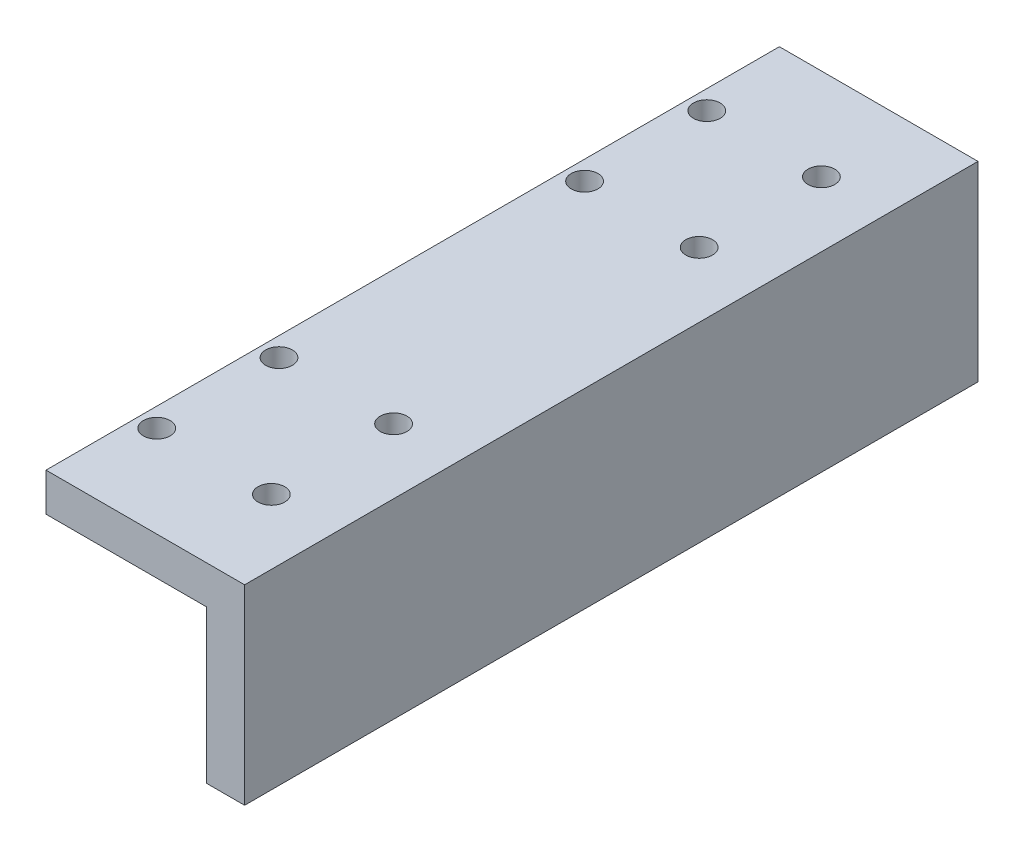
SolidWorks part; units mm, degrees
ref_plane "Front Plane" through (0, 0, 0) normal (0, 0, 1) x (1, 0, 0)
ref_plane "Top Plane" through (0, 0, 0) normal (0, 1, 0) x (1, 0, 0)
ref_plane "Right Plane" through (0, 0, 0) normal (1, 0, 0) x (0, 0, -1)
sketch "Sketch1" plane through (0, 0, 0) normal (0, 1, 0) x (1, 0, 0)
  line L0 (0, 48) -> (0, -48) construction
  line L1 (-10, 48) -> (10, 48)
  line L2 (-10, 48) -> (-10, -48)
  line L3 (-10, -48) -> (10, -48)
  line L4 (10, 48) -> (10, -48) construction
  line L5 (-10, 48) -> (10, -48) construction
  line L6 (-10, -48) -> (10, 48) construction
  line L7 (-7.5, 36) -> (7.5, 36) construction
  line L8 (-7.5, 36) -> (7.5, 20) construction
  line L9 (-10, 0) -> (10, 0) construction
  line L10 (-7.5, -36) -> (7.5, -20) construction
  line L11 (-7.5, -36) -> (7.5, -36) construction
  line L12 (-7.5, 20) -> (7.5, 20) construction
  line L13 (10, 48) -> (11, 48)
  line L14 (11, 48) -> (11, -48)
  line L15 (11, -48) -> (10, -48)
  circle A0 centre (-7.5, 36) radius 1.75
  circle A1 centre (7.5, 36) radius 1.75
  circle A2 centre (-7.5, 20) radius 1.75
  circle A3 centre (7.5, 20) radius 1.75
  circle A4 centre (7.5, -20) radius 1.75
  circle A5 centre (-7.5, -20) radius 1.75
  circle A6 centre (7.5, -36) radius 1.75
  circle A7 centre (-7.5, -36) radius 1.75
  point P0 (0, 0)
  point P16 (0, 36)
  dimension "D2" = 3.5
  dimension "D1" = 20
  dimension "D3" = 15
  dimension "D4" = 16
  dimension "D5" = 12
  dimension "D6" = 20
  dimension "D7" = 1
extrude "Boss-Extrude1" add sketch "Sketch1" along normal blind 5
sketch "Sketch2" plane through (11, 0, 0) normal (1, 0, 0) x (0, 0, -1)
  line L1 (-48, 5) -> (48, 5)
  line L2 (-48, 5) -> (-48, -20)
  line L3 (-48, -20) -> (48, -20)
  line L5 (48, 5) -> (48, -20)
  line L6 (48, 5) -> (48, 0) construction
  line L7 (-48, 5) -> (-48, 0) construction
  line L8 (-48, 5) -> (48, 5) construction
  point P7 (0, 0)
  dimension "D1" = 25
extrude "Boss-Extrude2" add sketch "Sketch2" along normal blind 5
